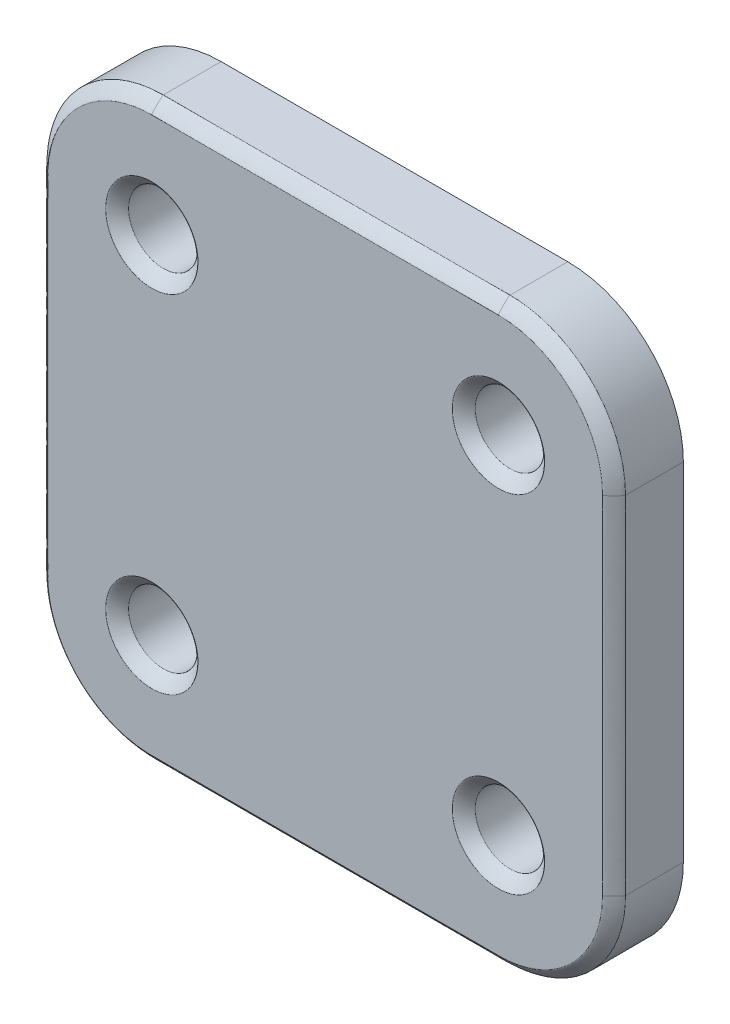
SolidWorks part; units mm, degrees
ref_plane "Plan de face" through (0, 0, 0) normal (0, 0, 1) x (1, 0, 0)
ref_plane "Plan de dessus" through (0, 0, 0) normal (0, 1, 0) x (1, 0, 0)
ref_plane "Plan de droite" through (0, 0, 0) normal (1, 0, 0) x (0, 0, -1)
sketch "Esquisse1" plane through (0, 0, 0) normal (0, 0, 1) x (1, 0, 0)
  line L0 (-7.5, 7.5) -> (7.5, 7.5) construction
  line L1 (7.5, -12.5) -> (-7.5, -12.5)
  line L2 (12.5, -7.5) -> (12.5, 7.5)
  line L3 (7.5, 12.5) -> (-7.5, 12.5)
  line L4 (-12.5, -7.5) -> (-12.5, 7.5)
  line L5 (12.5, -12.5) -> (-12.5, 12.5) construction
  line L6 (12.5, 12.5) -> (-12.5, -12.5) construction
  line L7 (-7.5, -7.5) -> (-7.5, 7.5) construction
  arc A0 (-7.5, -12.5) -> (-12.5, -7.5) centre (-7.5, -7.5) cw
  arc A1 (7.5, -12.5) -> (12.5, -7.5) centre (7.5, -7.5) ccw
  arc A2 (12.5, 7.5) -> (7.5, 12.5) centre (7.5, 7.5) ccw
  arc A3 (-7.5, 12.5) -> (-12.5, 7.5) centre (-7.5, 7.5) ccw
  circle A5 centre (-7.5, 7.5) radius 1.5
  circle A6 centre (7.5, 7.5) radius 1.5
  circle A7 centre (7.5, -7.5) radius 1.5
  circle A8 centre (-7.5, -7.5) radius 1.5
  point P0 (0, 0)
  dimension "D2" = 5
  dimension "D3" = 3
  dimension "D1" = 25
  dimension "D4" = 2
  dimension "D5" = 2
extrude "Boss.-Extru.1" add sketch "Esquisse1" along normal blind 3
fillet "Congé1" radius 0.5 12 edges at (-6, -7.5, 3) (9, -7.5, 3) (9, 7.5, 3) (-6, 7.5, 3) (-12.5, 0, 3) (-11.0355, 11.0355, 3) (0, 12.5, 3) (11.0355, 11.0355, 3) (12.5, 0, 3) (11.0355, -11.0355, 3) (0, -12.5, 3) (-11.0355, -11.0355, 3) conic rho 0.1
